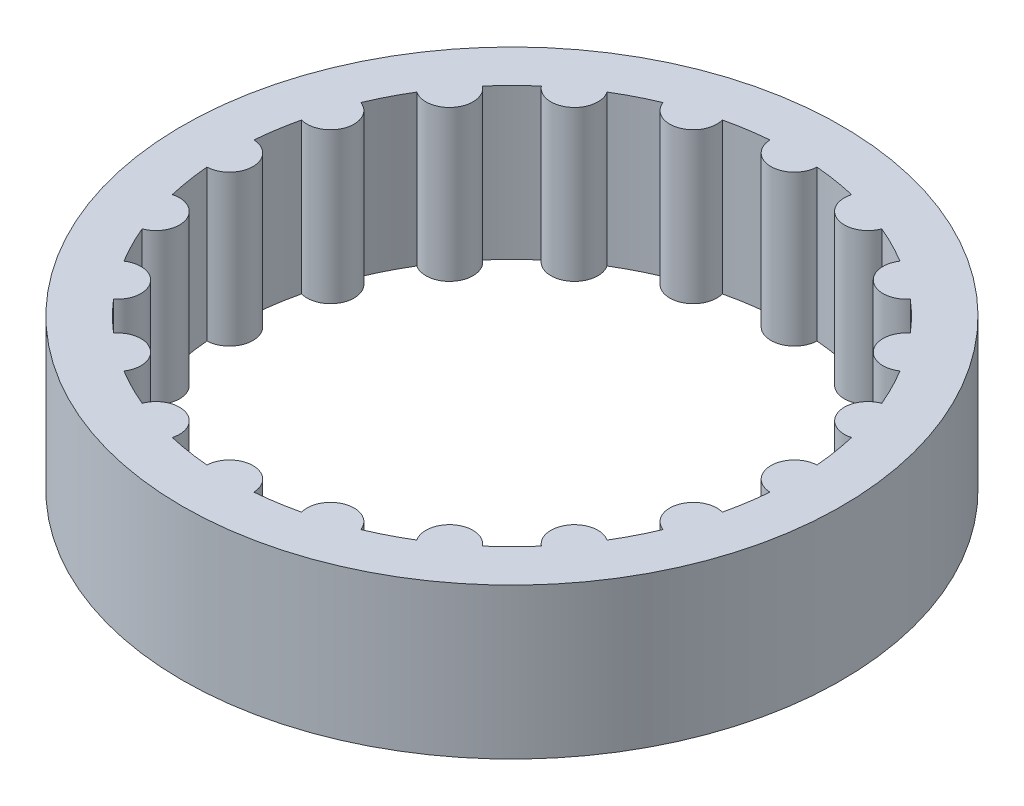
SolidWorks part; units mm, degrees
ref_plane "Front Plane" through (0, 0, 0) normal (0, 0, 1) x (1, 0, 0)
ref_plane "Top Plane" through (0, 0, 0) normal (0, 1, 0) x (1, 0, 0)
ref_plane "Right Plane" through (0, 0, 0) normal (1, 0, 0) x (0, 0, -1)
sketch "MAIN" plane through (0, 0, 0) normal (0, 1, 0) x (1, 0, 0)
  line L0 (-28.5, 0) -> (26.1, 0) construction
  circle A0 centre (-1.2, 0) radius 30
  circle A1 centre (28.8, 0) radius 2.5
  circle A2 centre (27.3317, -9.2705) radius 2.5
  circle A3 centre (23.0705, -17.6336) radius 2.5
  circle A4 centre (16.4336, -24.2705) radius 2.5
  circle A5 centre (8.0705, -28.5317) radius 2.5
  circle A6 centre (-1.2, -30) radius 2.5
  circle A7 centre (-10.4705, -28.5317) radius 2.5
  circle A8 centre (-18.8336, -24.2705) radius 2.5
  circle A9 centre (-25.4705, -17.6336) radius 2.5
  circle A10 centre (-29.7317, -9.2705) radius 2.5
  circle A11 centre (-31.2, 0) radius 2.5
  circle A12 centre (-29.7317, 9.2705) radius 2.5
  circle A13 centre (-25.4705, 17.6336) radius 2.5
  circle A14 centre (-18.8336, 24.2705) radius 2.5
  circle A15 centre (-10.4705, 28.5317) radius 2.5
  circle A16 centre (-1.2, 30) radius 2.5
  circle A17 centre (8.0705, 28.5317) radius 2.5
  circle A18 centre (16.4336, 24.2705) radius 2.5
  circle A19 centre (23.0705, 17.6336) radius 2.5
  circle A20 centre (27.3317, 9.2705) radius 2.5
  circle A21 centre (-1.2, 0) radius 35
  dimension "D1" = 5
  dimension "D2" = 60
  dimension "D4" = 70
  dimension "D3" = 20
extrude "Boss-Extrude1" add sketch "MAIN" along normal blind 8 and the other way blind 8 contours A21 A20 A0 A1 A2 A3 A4 A5 A6 A7 A8 A9 A10 A11 A12 A13 A14 A15 A16 A17 A18 A19 | A0 A12 | A0 A11 | A0 A10 | A0 A9 | A0 A9 | A0 A10 | A0 A11 | A0 A12 | A0 A13 | A0 A13 | A0 A14 | A0 A14 | A15 | A16 | A17 | A18 | A19 | A20 | A1 | A2 | A3 | A4 | A5 | A6 | A7 | A8 region at (-18.199, 0, -23.3971) region at (-19.4461, 0, -25.1135) region at (-24.5971, 0, -16.999) region at (-26.3135, 0, -18.2461) region at (-26.3135, 0, 18.2461) region at (-24.5971, 0, 16.999) region at (-28.705, 0, -8.9369) region at (-30.7227, 0, -9.5925) region at (-30.7227, 0, 9.5925) region at (-28.705, 0, 8.9369) region at (-30.1204, 0, 0) region at (-32.242, 0, 0) region at (-35.2101, 0, 0)
